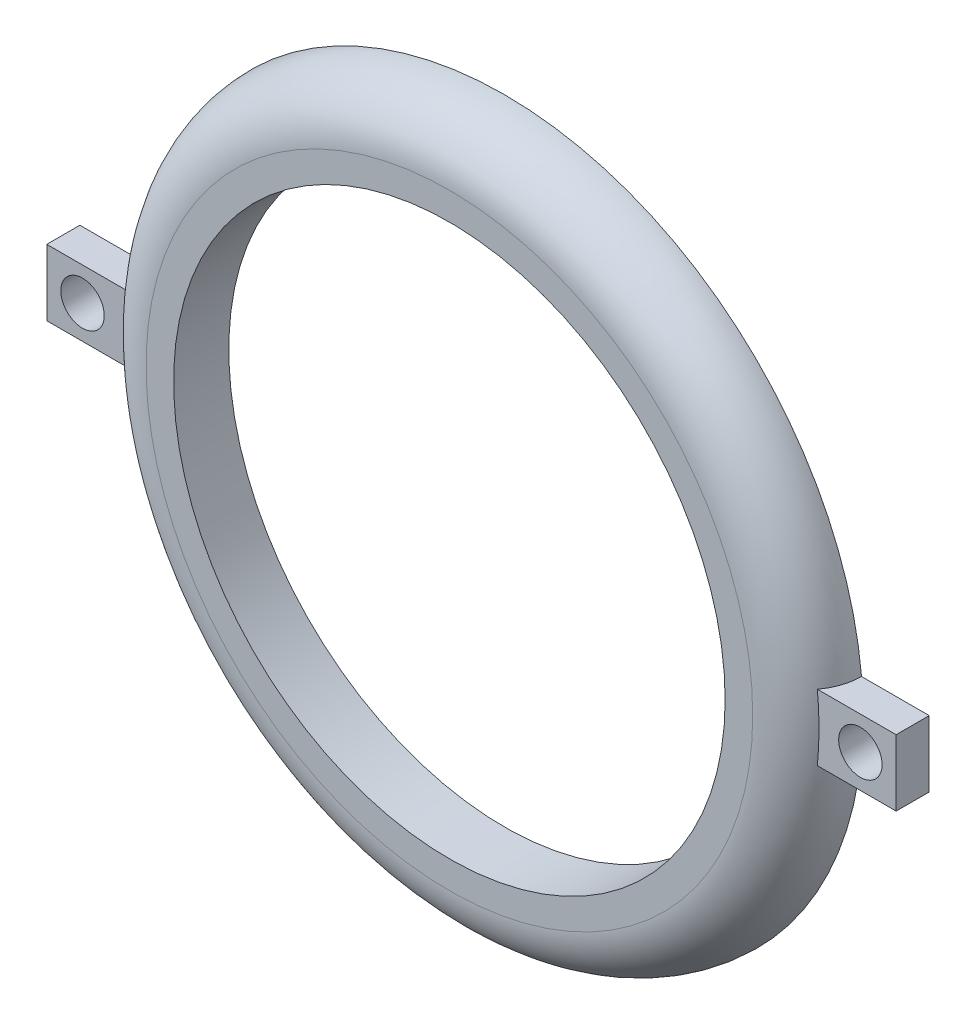
SolidWorks part; units mm, degrees
ref_plane "Front Plane" through (0, 0, 0) normal (0, 0, 1) x (1, 0, 0)
ref_plane "Top Plane" through (0, 0, 0) normal (0, 1, 0) x (1, 0, 0)
ref_plane "Right Plane" through (0, 0, 0) normal (1, 0, 0) x (0, 0, -1)
sketch "Sketch1" plane through (0, 0, 0) normal (0, 0, 1) x (1, 0, 0)
  circle A0 centre (0, 0) radius 16.51
  circle A1 centre (0, 0) radius 12.7
  dimension "D1" = 33.02
  dimension "D2" = 25.4
extrude "Boss-Extrude1" add sketch "Sketch1" along normal blind 2.54
ref_plane "Plane1" through (-16.51, 0, 0) normal (-1, 0, 0) x (0, 0, 1)
sketch "Sketch4" plane through (-16.51, 0, 0) normal (-1, 0, 0) x (0, 0, 1)
  line L0 (0, -1.524) -> (0, 1.524)
  line L1 (0, 16.51) -> (0, -16.51) construction
  line L2 (0, 1.524) -> (1.524, 1.524)
  line L3 (1.524, 1.524) -> (1.524, -1.524)
  line L4 (1.524, -1.524) -> (0, -1.524)
  point P5 (0, 0)
  dimension "D1" = 1.524
  dimension "D2" = 3.048
extrude "Boss-Extrude2" add sketch "Sketch4" against normal up to surface and the other way blind 3.048 up to face at (16.51, 0, 2.54)
mirror "Mirror2" about plane through (0, 0, 0) normal (1, 0, 0) of "Boss-Extrude2"
fillet "Fillet3" radius 2.54 1 edges at (16.51, 0, 2.54)
sketch "Sketch5" plane through (0, 0, 1.524) normal (0, 0, 1) x (1, 0, 0)
  line L0 (-19.558, 1.524) -> (-15.9293, 1.524) construction
  line L1 (-19.558, -1.524) -> (-19.558, 1.524) construction
  circle A0 centre (-17.9113, 0) radius 1
  point P2 (-17.9113, 0)
  dimension "D1" = 2
  dimension "D2" = 1.524
  dimension "D3" = 1.6467
extrude "Cut-Extrude1" cut sketch "Sketch5" against normal blind 2.54
mirror "Mirror3" about plane through (0, 0, 0) normal (1, 0, 0) of "Cut-Extrude1"
